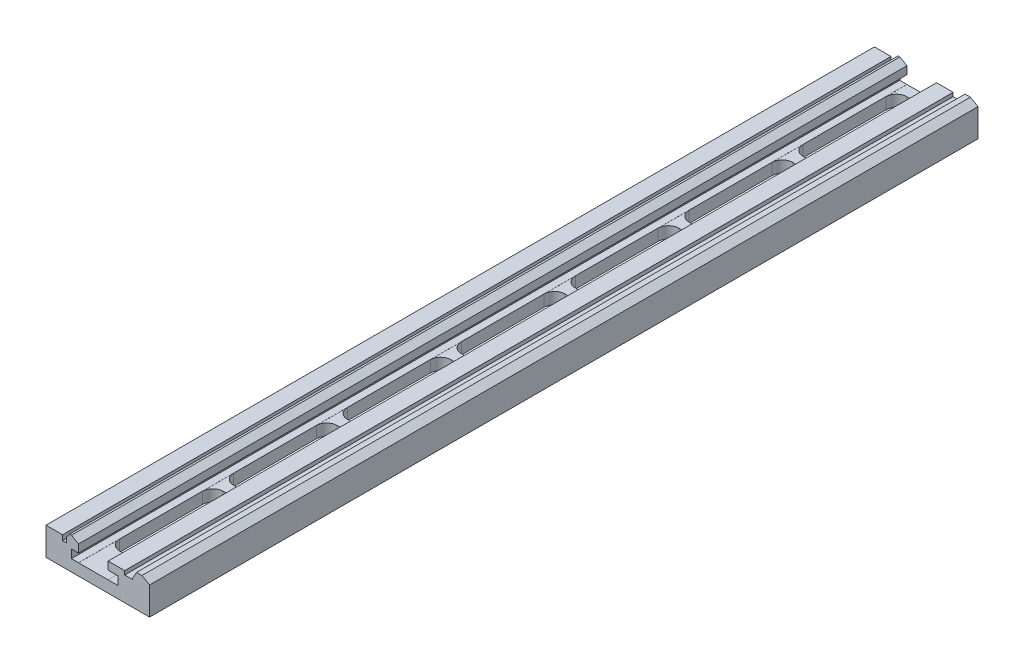
SolidWorks part; units mm, degrees
ref_plane "Front Plane" through (0, 0, 0) normal (0, 0, 1) x (1, 0, 0)
ref_plane "Top Plane" through (0, 0, 0) normal (0, 1, 0) x (1, 0, 0)
ref_plane "Right Plane" through (0, 0, 0) normal (1, 0, 0) x (0, 0, -1)
sketch "Sketch1" plane through (0, 0, 0) normal (0, 0, 1) x (1, 0, 0)
  line L0 (-31.7807, 35.4651) -> (-39.1312, 39.7065)
  line L2 (-131.7807, 35.4651) -> (-131.7807, 8.5548)
  line L3 (-131.7807, 8.5548) -> (-31.7807, 8.5548)
  line L4 (-31.7807, 35.4651) -> (-31.7807, 8.5548)
  line L5 (-39.1312, 39.7065) -> (-44.3271, 39.7065)
  line L6 (-44.3271, 39.7065) -> (-48.4627, 32.5393)
  line L7 (-48.4627, 32.5393) -> (-48.4627, 31.8106)
  line L8 (-48.4627, 31.8106) -> (-55.7807, 31.8106)
  line L9 (-55.7807, 31.8106) -> (-55.7807, 35.4651)
  line L10 (-55.7807, 35.4651) -> (-71.7807, 35.4651)
  line L11 (-71.7807, 35.4651) -> (-71.7807, 19.6844)
  line L12 (-71.7807, 19.6844) -> (-100.3854, 19.6844)
  line L13 (-100.3854, 19.6844) -> (-100.3854, 35.4651)
  line L14 (-100.3854, 35.4651) -> (-107.1606, 39.3745)
  line L15 (-107.1606, 39.3745) -> (-109.0021, 39.3745)
  line L16 (-109.0021, 39.3745) -> (-111.7807, 35.4651)
  line L17 (-111.7807, 35.4651) -> (-111.7807, 30.4817)
  line L18 (-111.7807, 30.4817) -> (-115.7807, 30.4817)
  line L19 (-115.7807, 30.4817) -> (-115.7807, 35.4651)
  line L20 (-115.7807, 35.4651) -> (-131.7807, 35.4651)
  dimension "D1" = 100
  dimension "D2" = 31.3953
  dimension "D3" = 60
  dimension "D4" = 16
  dimension "D5" = 16
  dimension "D6" = 4
extrude "Boss-Extrude1" add sketch "Sketch1" along normal blind 800
sketch "Sketch2" plane through (0, 19.6844, 0) normal (0, 1, 0) x (1, 0, 0)
  line L0 (-100.3854, -800) -> (-100.3854, 0) construction
  line L1 (-90.3854, -10.2914) -> (-81.7807, -10.2914)
  line L2 (-100.3854, -20.2914) -> (-100.3854, -100.2914)
  line L3 (-90.3854, -110.2914) -> (-81.7807, -110.2914)
  line L4 (-71.7807, -20.2914) -> (-71.7807, -100.2914)
  line L5 (-71.7807, -800) -> (-71.7807, 0) construction
  arc A0 (-100.3854, -100.2914) -> (-90.3854, -110.2914) centre (-90.3854, -100.2914) ccw
  arc A1 (-81.7807, -110.2914) -> (-71.7807, -100.2914) centre (-81.7807, -100.2914) ccw
  arc A2 (-81.7807, -10.2914) -> (-71.7807, -20.2914) centre (-81.7807, -20.2914) cw
  arc A3 (-90.3854, -10.2914) -> (-100.3854, -20.2914) centre (-90.3854, -20.2914) ccw
  point P12 (-71.7807, -110.2914)
  point P15 (-71.7807, -10.2914)
  point P18 (-100.3854, -10.2914)
  dimension "D2" = 10
  dimension "D1" = 100
extrude "Cut-Extrude1" cut sketch "Sketch2" against normal blind 800
pattern_linear "LPattern1" count 7 spacing 110 along (0, 0, 1) of "Cut-Extrude1"
sketch "Sketch3" plane through (0, 0, 800) normal (0, 0, 1) x (1, 0, 0)
  line L1 (-62.4385, 19.762) -> (-107.2592, 19.762)
  line L2 (-62.4385, 19.762) -> (-62.4385, 27.8324)
  line L3 (-62.4385, 27.8324) -> (-107.2592, 27.8324)
  line L4 (-107.2592, 19.762) -> (-107.2592, 27.8324)
extrude "Cut-Extrude2" cut sketch "Sketch3" against normal blind 800
